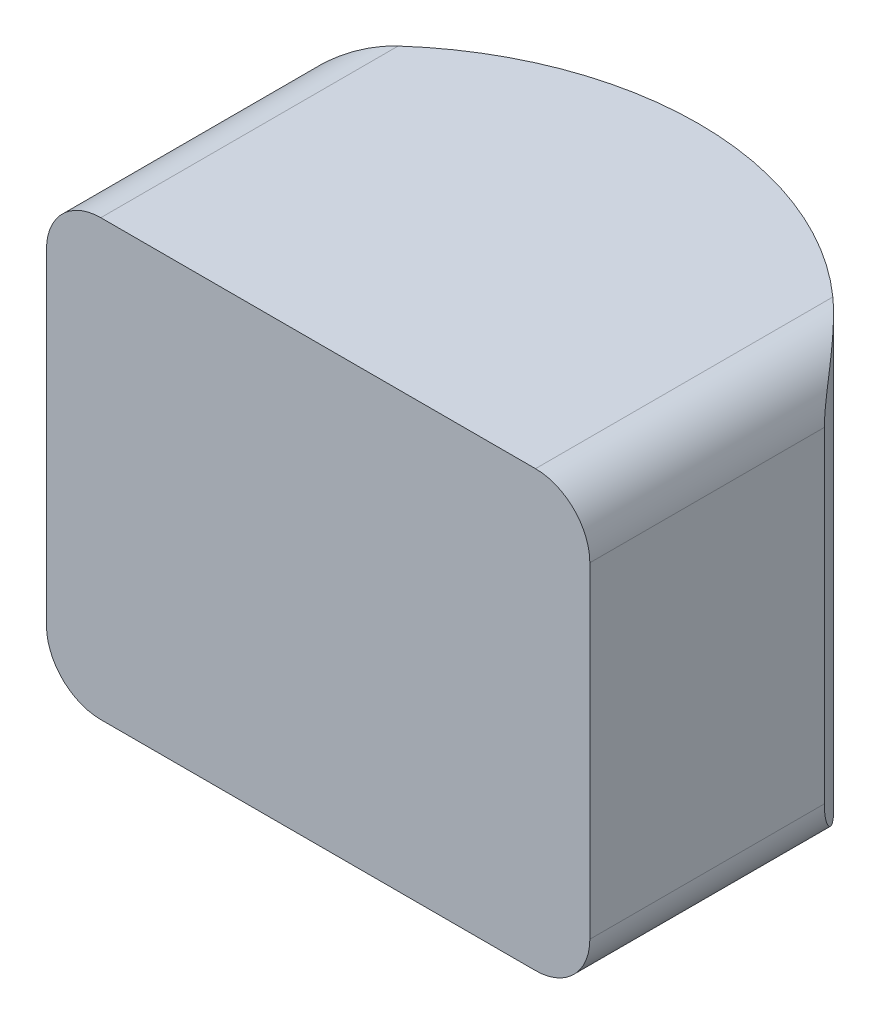
SolidWorks part; units mm, degrees
ref_plane "Front Plane" through (0, 0, 0) normal (0, 0, 1) x (1, 0, 0)
ref_plane "Top Plane" through (0, 0, 0) normal (0, 1, 0) x (1, 0, 0)
ref_plane "Right Plane" through (0, 0, 0) normal (1, 0, 0) x (0, 0, -1)
sketch "Croquis1" plane through (0, 0, 0) normal (0, 0, 1) x (1, 0, 0)
  line L1 (-4, 4) -> (4, 4)
  line L2 (-5, 3) -> (-5, -3)
  line L3 (-4, -4) -> (4, -4)
  line L4 (5, 3) -> (5, -3)
  line L5 (-5, 4) -> (5, -4) construction
  line L6 (-5, -4) -> (5, 4) construction
  arc A0 (4, 4) -> (5, 3) centre (4, 3) cw
  arc A1 (4, -4) -> (5, -3) centre (4, -3) ccw
  arc A2 (-5, -3) -> (-4, -4) centre (-4, -3) ccw
  arc A3 (-4, 4) -> (-5, 3) centre (-4, 3) ccw
  point P0 (0, 0)
  point P6 (0, 0)
  dimension "D3" = 1
  dimension "D1" = 10
  dimension "D2" = 8
ref_plane "Plano1" through (0, 0, 6) normal (0, 0, 1) x (1, 0, 0)
extrude "Saliente-Extruir1" add sketch "Croquis1" against normal blind 1
sketch "Croquis2" plane through (0, 0, 0) normal (0, 1, 0) x (1, 0, 0)
  line L0 (0, 1) -> (-6, 1)
  line L1 (0, 0) -> (0, 19.5223) construction
  line L4 (4, 0) -> (-4, 0) construction
  line L6 (0, 1) -> (6, 1)
  line L7 (4, 1) -> (-4, 1) construction
  line L8 (0, 1) -> (0, 7) construction
  arc A1 (0, 7) -> (-6, 1) centre (0, 1) ccw
  arc A2 (0, 7) -> (6, 1) centre (0, 1) cw
  dimension "D1" = 6
extrude "Saliente-Extruir2" add sketch "Croquis2" against normal mid plane 14
sketch "Croquis4" plane through (0, 0, 0) normal (0, 0, 1) x (1, 0, 0)
  line L0 (5, -3) -> (5, 3) construction
  line L1 (-4, -4) -> (4, -4) construction
  line L2 (-5, 3) -> (-5, -3) construction
  line L3 (4, 4) -> (-4, 4) construction
  line L4 (5, -3) -> (5, 3)
  line L5 (-4, -4) -> (4, -4)
  line L6 (-5, 3) -> (-5, -3)
  line L7 (4, 4) -> (-4, 4)
  line L8 (-10.5074, 10.0455) -> (11.2559, 10.0455)
  line L9 (11.2559, 10.0455) -> (11.2559, -10.4601)
  line L10 (11.2559, -10.4601) -> (-10.5074, -10.4601)
  line L11 (-10.5074, -10.4601) -> (-10.5074, 10.0455)
  arc A0 (5, 3) -> (4, 4) centre (4, 3) ccw construction
  arc A1 (4, -4) -> (5, -3) centre (4, -3) ccw construction
  arc A2 (-5, -3) -> (-4, -4) centre (-4, -3) ccw construction
  arc A3 (-4, 4) -> (-5, 3) centre (-4, 3) ccw construction
  arc A4 (5, 3) -> (4, 4) centre (4, 3) ccw
  arc A5 (4, -4) -> (5, -3) centre (4, -3) ccw
  arc A6 (-5, -3) -> (-4, -4) centre (-4, -3) ccw
  arc A7 (-4, 4) -> (-5, 3) centre (-4, 3) ccw
extrude "Cortar-Extruir1" cut sketch "Croquis4" against normal blind 14
